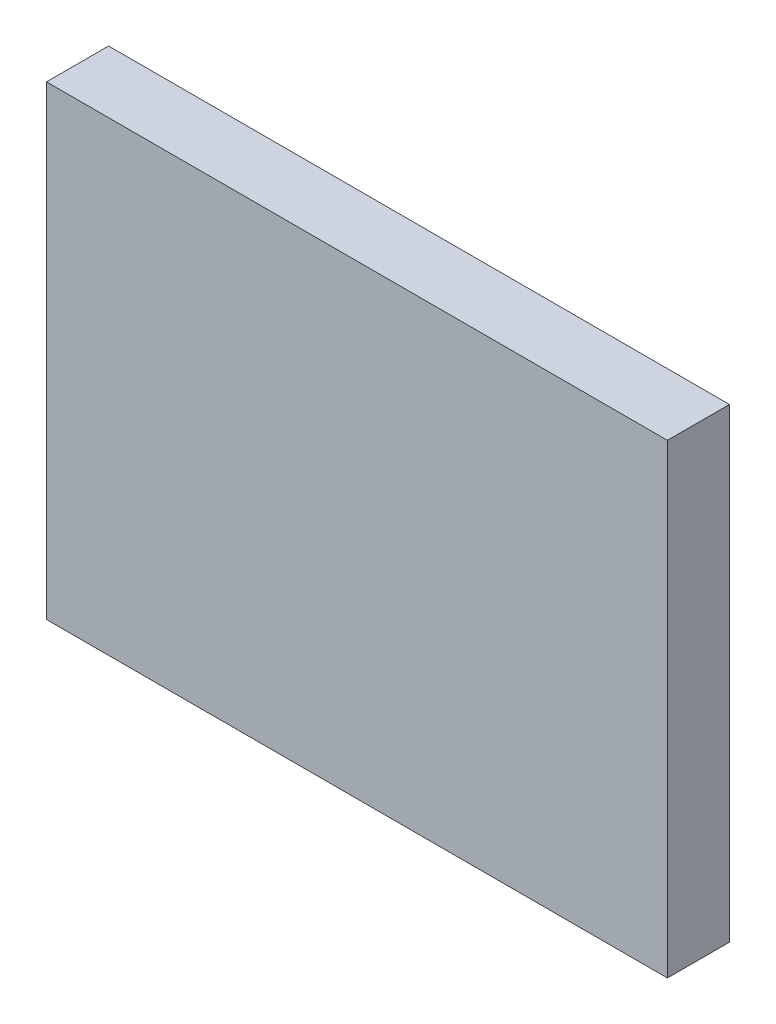
SolidWorks part; units mm, degrees
ref_plane "Front Plane" through (0, 0, 0) normal (0, 0, 1) x (1, 0, 0)
ref_plane "Top Plane" through (0, 0, 0) normal (0, 1, 0) x (1, 0, 0)
ref_plane "Right Plane" through (0, 0, 0) normal (1, 0, 0) x (0, 0, -1)
sketch "Sketch1" plane through (0, 0, 0) normal (0, 0, 1) x (1, 0, 0)
  line L1 (0, 0) -> (60, 0)
  line L2 (0, 0) -> (0, 45)
  line L3 (0, 45) -> (60, 45)
  line L4 (60, 0) -> (60, 45)
  dimension "D1" = 45
  dimension "D2" = 60
extrude "Boss-Extrude1" add sketch "Sketch1" along normal blind 6
